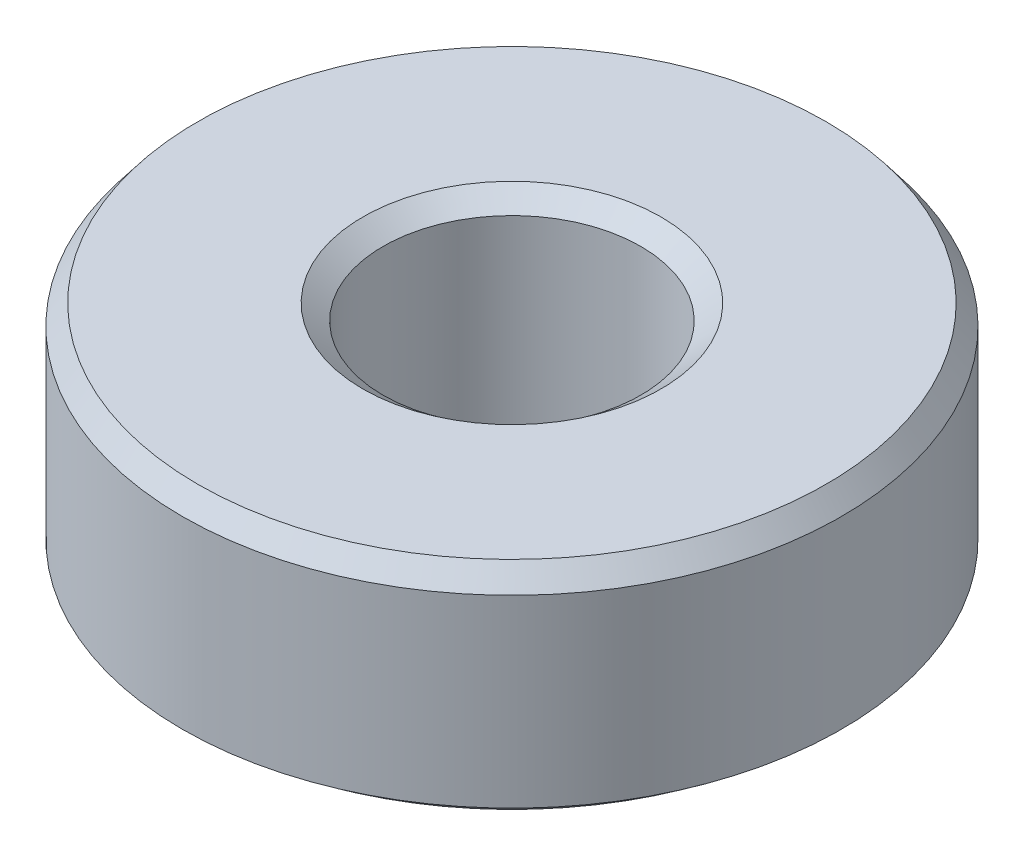
SolidWorks part; units mm, degrees
ref_plane "Front Plane" through (0, 0, 0) normal (0, 0, 1) x (1, 0, 0)
ref_plane "Top Plane" through (0, 0, 0) normal (0, 1, 0) x (1, 0, 0)
ref_plane "Right Plane" through (0, 0, 0) normal (1, 0, 0) x (0, 0, -1)
sketch "Sketch1" plane through (0, 0, 0) normal (0, 1, 0) x (1, 0, 0)
  circle A0 centre (0, 0) radius 60
  dimension "SLEEVE_OD" = 120
extrude "Boss-Extrude1" add sketch "Sketch1" along normal blind 40.0359
sketch "Sketch2" plane through (0, 0, 0) normal (0, 1, 0) x (1, 0, 0)
  circle A0 centre (0, 0) radius 23.4689
  dimension "BORE_D" = 46.9378
extrude "Cut-Extrude1" cut sketch "Sketch2" along normal through all
chamfer "Chamfer1" distance 3.6699 angle 37.455 4 edges at (0, 40.0359, 23.4689) (0, 0, 23.4689) (0, 0, 60) (0, 40.0359, 60) first distance on face at (0, 40.0359, 23.4689) first distance on face at (0, 0, 23.4689) first distance on face at (0, 40.0359, 60)
